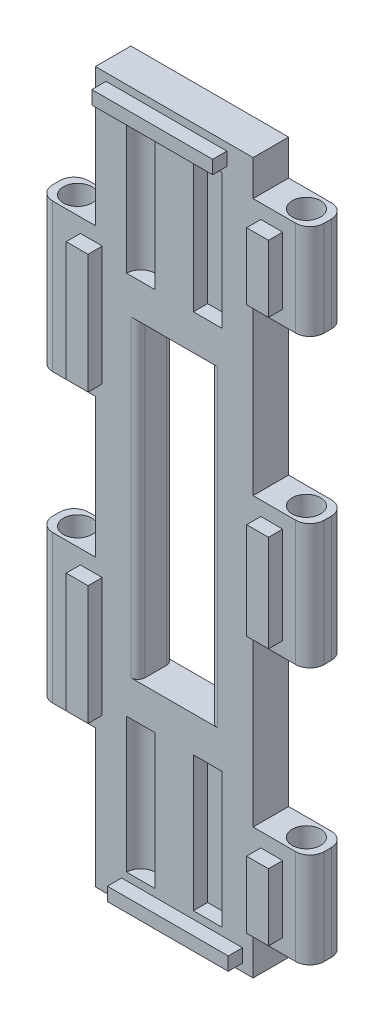
SolidWorks part; units mm, degrees
ref_plane "Ebene vorne" through (0, 0, 0) normal (0, 0, 1) x (1, 0, 0)
ref_plane "Ebene oben" through (0, 0, 0) normal (0, 1, 0) x (1, 0, 0)
ref_plane "Ebene rechts" through (0, 0, 0) normal (1, 0, 0) x (0, 0, -1)
sketch "Skizze1" plane through (0, 0, 0) normal (0, 0, 1) x (1, 0, 0)
  line L0 (-15.1, 49.2206) -> (-15.1, -0.7794)
  line L1 (-15.1, -0.7794) -> (-4, -0.7794)
  line L2 (-4, -0.7794) -> (-4, 49.2206)
  line L3 (-4, 49.2206) -> (-15.1, 49.2206)
  line L4 (-15.1, 39.5206) -> (-19.1, 39.5206)
  line L5 (-19.1, 39.5206) -> (-19.1, 29.1206)
  line L6 (-19.1, 29.1206) -> (-15.1, 29.1206)
  line L7 (-15.1, 8.9206) -> (-19.1, 8.9206)
  line L8 (-19.1, 8.9206) -> (-19.1, 19.3206)
  line L9 (-19.1, 19.3206) -> (-15.1, 19.3206)
  line L10 (-4, 8.4206) -> (0, 8.4206)
  line L11 (0, 8.4206) -> (0, 1.7206)
  line L12 (0, 1.7206) -> (-4, 1.7206)
  line L13 (-4, 40.0206) -> (0, 40.0206)
  line L14 (0, 40.0206) -> (0, 46.7206)
  line L15 (0, 46.7206) -> (-4, 46.7206)
  line L16 (-4, 28.6206) -> (0, 28.6206)
  line L17 (0, 28.6206) -> (0, 19.8206)
  line L18 (0, 19.8206) -> (-4, 19.8206)
  dimension "D2" = 11.1
  dimension "D3" = 0.5
  dimension "D4" = 6.7
  dimension "D5" = 0.5
  dimension "D6" = 50
  dimension "D7" = 0.5
  dimension "D8" = 4
  dimension "D9" = 11.4
  dimension "1" = 6.7
  dimension "D10" = 4
  dimension "D11" = 2.5
  dimension "D12" = 8.8
  dimension "D13" = 2.5
  dimension "D14" = 0.5
  dimension "D15" = 4
  dimension "D16" = 4
extrude "Aufsatz-Linear austragen1" add sketch "Skizze1" along normal blind 2.5 contours L9 L8 L7 L0 | L2 L3 L0 L1 | L5 L6 L0 L4 | L14 L15 L2 L13 | L12 L11 L10 L2 | L17 L2 region at (-9.55, 24.2206, 0) region at (-17.1, 34.3206, 0) region at (-2, 43.3706, 0) region at (-17.1, 14.1206, 0) region at (-2, 24.2206, 0) region at (-2, 5.0706, 0)
sketch "Skizze2" plane through (0, 39.5206, 0) normal (0, 1, 0) x (1, 0, 0)
  line L0 (-15.1, 0) -> (-19.1, 0) construction
  line L3 (-19.1, -2.5) -> (-19.1, 0) construction
  line L4 (0, 0) -> (-4, 0) construction
  line L5 (0, -2.5) -> (0, 0) construction
  circle A0 centre (-17.6, -1.25) radius 1
  circle A1 centre (-1.5, -1.25) radius 0.9978
  dimension "D1" = 2
  dimension "D2" = 1.25
  dimension "D4" = 1.25
  dimension "D5" = 1.5
  dimension "D3" = 1.5
extrude "Schnitt-Linear austragen1" cut sketch "Skizze2" along normal blind 37.5 and the other way blind 67.5
sketch "Skizze3" plane through (0, 0, 2.5) normal (0, 0, 1) x (1, 0, 0)
  line L0 (-12.1, 13.2206) -> (-12.1, 35.2206)
  line L1 (-12.1, 35.2206) -> (-7, 35.2206)
  line L2 (-7, 35.2206) -> (-7, 13.2206)
  line L3 (-7, 13.2206) -> (-12.1, 13.2206)
  line L4 (-15.1, -0.7794) -> (-4, -0.7794) construction
  line L5 (-15.1, 29.1206) -> (-15.1, 19.3206) construction
  line L6 (-4, 8.4206) -> (-4, 19.8206) construction
  point P6 (-9.55, -0.7794)
  dimension "D1" = 22
  dimension "D2" = 14
  dimension "D3" = 3
  dimension "D4" = 3
extrude "Schnitt-Linear austragen2" cut sketch "Skizze3" against normal blind 7.5
fillet "Verrundung3" radius 0.5 4 edges at (-7, 24.2206, 2.5) (-12.1, 24.2206, 2.5) (-12.1, 24.2206, 0) (-7, 24.2206, 0)
fillet "Verrundung4" radius 1 10 edges at (0, 43.3706, 0) (0, 43.3706, 2.5) (0, 24.2206, 0) (0, 24.2206, 2.5) (0, 5.0706, 0) (0, 5.0706, 2.5) (-19.1, 14.1206, 0) (-19.1, 14.1206, 2.5) (-19.1, 34.3206, 0) (-19.1, 34.3206, 2.5)
sketch "Skizze4" plane through (0, 0, 2.5) normal (0, 0, 1) x (1, 0, 0)
  line L0 (-12.9, 47.2206) -> (-12.9, 37.7206)
  line L1 (-12.9, 37.7206) -> (-10.9, 37.7206)
  line L2 (-10.9, 37.7206) -> (-10.9, 47.2206)
  line L3 (-10.9, 47.2206) -> (-12.9, 47.2206)
  line L4 (-12.9, 10.7206) -> (-12.9, 1.2206)
  line L5 (-12.9, 1.2206) -> (-10.9, 1.2206)
  line L6 (-10.9, 1.2206) -> (-10.9, 10.7206)
  line L7 (-10.9, 10.7206) -> (-12.9, 10.7206)
  line L9 (-15.1, 8.9206) -> (-15.1, -0.7794) construction
  line L10 (-12.6, 13.2206) -> (-6.5, 13.2206) construction
  line L13 (-6.5, 35.2206) -> (-12.6, 35.2206) construction
  line L14 (-8.2, 47.2206) -> (-8.2, 37.7206)
  line L15 (-8.2, 37.7206) -> (-6.2, 37.7206)
  line L16 (-6.2, 37.7206) -> (-6.2, 47.2206)
  line L17 (-6.2, 47.2206) -> (-8.2, 47.2206)
  line L18 (-8.2, 10.7206) -> (-8.2, 1.2206)
  line L19 (-8.2, 1.2206) -> (-6.2, 1.2206)
  line L20 (-6.2, 1.2206) -> (-6.2, 10.7206)
  line L21 (-6.2, 10.7206) -> (-8.2, 10.7206)
  line L22 (-4, 8.4206) -> (-4, 19.8206) construction
  dimension "D1" = 9.5
  dimension "D2" = 2.5
  dimension "D3" = 2.2
  dimension "D4" = 2.5
  dimension "D5" = 9.5
  dimension "D6" = 2.2
  dimension "D7" = 2
  dimension "D8" = 2
  dimension "D9" = 2
  dimension "D10" = 2
  dimension "D11" = 2.5
  dimension "D12" = 2.5
  dimension "D13" = 9.5
  dimension "D14" = 9.5
extrude "Schnitt-Linear austragen3" cut sketch "Skizze4" against normal blind 1
fillet "Verrundung5" radius 1 4 edges at (-6.2, 5.9706, 1.5) (-12.9, 5.9706, 1.5) (-12.9, 42.4706, 1.5) (-6.2, 42.4706, 1.5)
sketch "Skizze7" plane through (0, 0, 2.5) normal (0, 0, 1) x (1, 0, 0)
  line L0 (-14.35, 48.6906) -> (-5.85, 48.6906)
  line L1 (-5.85, 48.6906) -> (-5.85, 47.7506)
  line L2 (-5.85, 47.7506) -> (-14.35, 47.7506)
  line L3 (-14.35, 47.7506) -> (-14.35, 48.6906)
  line L4 (-4, 49.2206) -> (-15.1, 49.2206) construction
  line L5 (-6.2, 47.2206) -> (-8.2, 47.2206) construction
  line L8 (-15.1, 49.2206) -> (-15.1, 39.5206) construction
  line L18 (-13.25, 0.6906) -> (-4.75, 0.6906)
  line L19 (-4.75, 0.6906) -> (-4.75, -0.2494)
  line L20 (-4.75, -0.2494) -> (-13.25, -0.2494)
  line L21 (-13.25, -0.2494) -> (-13.25, 0.6906)
  line L22 (-8.2, 1.2206) -> (-6.2, 1.2206) construction
  line L23 (-15.1, -0.7794) -> (-4, -0.7794) construction
  line L24 (-16.1544, 18.3206) -> (-16.1544, 9.9206)
  line L25 (-16.1544, 9.9206) -> (-14.6161, 9.9206)
  line L26 (-14.6161, 9.9206) -> (-14.6161, 18.3206)
  line L27 (-14.6161, 18.3206) -> (-16.1544, 18.3206)
  line L28 (-3.4546, 7.4206) -> (-3.4546, 2.7206)
  line L29 (-3.4546, 2.7206) -> (-1.9163, 2.7206)
  line L30 (-1.9163, 2.7206) -> (-1.9163, 7.4206)
  line L31 (-1.9163, 7.4206) -> (-3.4546, 7.4206)
  line L32 (-3.4546, 27.6206) -> (-3.4546, 20.8206)
  line L33 (-3.4546, 20.8206) -> (-1.9163, 20.8206)
  line L34 (-1.9163, 20.8206) -> (-1.9163, 27.6206)
  line L35 (-1.9163, 27.6206) -> (-3.4546, 27.6206)
  line L36 (-16.1544, 38.5206) -> (-16.1544, 30.1206)
  line L37 (-16.1544, 30.1206) -> (-14.6161, 30.1206)
  line L38 (-14.6161, 30.1206) -> (-14.6161, 38.5206)
  line L39 (-14.6161, 38.5206) -> (-16.1544, 38.5206)
  line L40 (-3.4546, 45.7206) -> (-3.4546, 41.0206)
  line L41 (-3.4546, 41.0206) -> (-1.9163, 41.0206)
  line L42 (-1.9163, 41.0206) -> (-1.9163, 45.7206)
  line L43 (-1.9163, 45.7206) -> (-3.4546, 45.7206)
  line L46 (-4, 40.0206) -> (-1, 40.0206) construction
  line L47 (-1, 46.7206) -> (-4, 46.7206) construction
  line L48 (-4, 28.6206) -> (-1, 28.6206) construction
  line L50 (-15.1, 39.5206) -> (-18.1, 39.5206) construction
  line L51 (-15.1, 8.9206) -> (-18.1, 8.9206) construction
  line L52 (-18.1, 19.3206) -> (-15.1, 19.3206) construction
  line L53 (-4, 8.4206) -> (-1, 8.4206) construction
  line L54 (-1, 1.7206) -> (-4, 1.7206) construction
  dimension "D1" = 0.53
  dimension "D2" = 0.53
  dimension "D3" = 8.5
  dimension "D4" = 0.75
  dimension "D5" = 0.53
  dimension "D6" = 0.53
  dimension "D7" = 1
  dimension "D8" = 1
  dimension "D9" = 1
  dimension "D10" = 1
  dimension "D11" = 1
  dimension "D12" = 1
  dimension "D13" = 1
  dimension "D14" = 1
  dimension "D15" = 1
  dimension "D16" = 1
extrude "Aufsatz-Linear austragen4" add sketch "Skizze7" along normal blind 1
